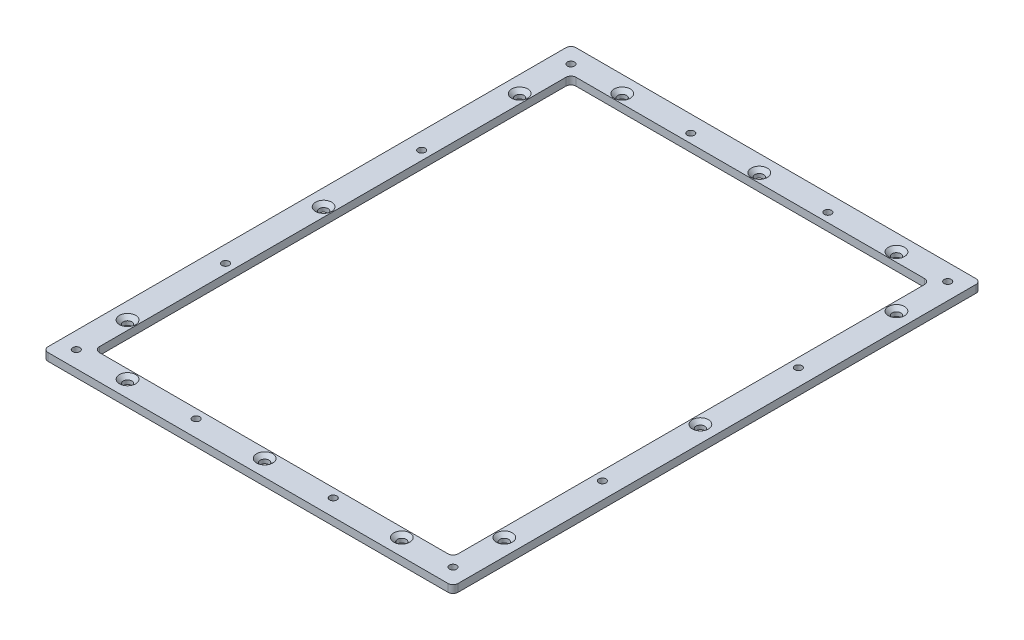
SolidWorks part; units mm, degrees
ref_plane "Front Plane" through (0, 0, 0) normal (0, 0, 1) x (1, 0, 0)
ref_plane "Top Plane" through (0, 0, 0) normal (0, 1, 0) x (1, 0, 0)
ref_plane "Right Plane" through (0, 0, 0) normal (1, 0, 0) x (0, 0, -1)
sketch "Sketch1" plane through (0, 0, 0) normal (0, 1, 0) x (1, 0, 0)
  line L0 (78, 103) -> (-78, 103) construction
  line L1 (-70, -93) -> (70, -93)
  line L2 (-70, -93) -> (-70, 93)
  line L3 (-70, 93) -> (70, 93)
  line L4 (70, -93) -> (70, 93)
  line L5 (-70, -93) -> (70, 93) construction
  line L6 (-70, 93) -> (70, -93) construction
  line L7 (80, -103) -> (-80, -103)
  line L8 (80, -103) -> (80, 103)
  line L9 (80, 103) -> (-80, 103)
  line L10 (-80, -103) -> (-80, 103)
  line L11 (80, -103) -> (-80, 103) construction
  line L12 (80, 103) -> (-80, -103) construction
  line L13 (-80, 101) -> (-80, -101) construction
  point P0 (0, 0)
  point P5 (0, 0)
  point P11 (-48.5964, 76.0062)
  point P12 (-80.7977, 104.555)
  dimension "D1" = 10
  dimension "D2" = 10
extrude "Boss-Extrude1" add sketch "Sketch1" along normal blind 3
ref_axis "Axis2" through (0, -0.3, 0) along (0, 1, 0)
fillet "Fillet1" radius 2 8 edges at (80, 1.5, -103) (80, 1.5, 103) (-80, 1.5, -103) (-80, 1.5, 103) (70, 1.5, -93) (70, 1.5, 93) (-70, 1.5, 93) (-70, 1.5, -93)
ref_plane "Plane1" through (78, 0, 0) normal (-1, 0, 0) x (0, 0, 1)
sketch "Sketch6" plane through (0, 0, 0) normal (0, -1, 0) x (1, 0, 0)
  line L9 (-78, -102) -> (78, -102)
  line L10 (79, -101) -> (79, 101)
  line L11 (78, 102) -> (-78, 102)
  line L12 (-79, 101) -> (-79, -101)
  line L13 (-78, -102) -> (78, -102)
  line L14 (79, -101) -> (79, 101)
  line L15 (78, 102) -> (-78, 102)
  line L16 (-79, 101) -> (-79, -101)
  line L21 (-78, -101.5) -> (78, -101.5)
  line L22 (78.5, -101) -> (78.5, 101)
  line L23 (78, 101.5) -> (-78, 101.5)
  line L24 (-78.5, 101) -> (-78.5, -101)
  line L25 (-78, -101.5) -> (78, -101.5)
  line L26 (78.5, -101) -> (78.5, 101)
  line L27 (78, 101.5) -> (-78, 101.5)
  line L28 (-78.5, 101) -> (-78.5, -101)
  arc A8 (78, -102) -> (79, -101) centre (78, -101) ccw
  arc A9 (79, 101) -> (78, 102) centre (78, 101) ccw
  arc A10 (-78, 102) -> (-79, 101) centre (-78, 101) ccw
  arc A11 (-79, -101) -> (-78, -102) centre (-78, -101) ccw
  arc A12 (78, -102) -> (79, -101) centre (78, -101) ccw
  arc A13 (79, 101) -> (78, 102) centre (78, 101) ccw
  arc A14 (-78, 102) -> (-79, 101) centre (-78, 101) ccw
  arc A15 (-79, -101) -> (-78, -102) centre (-78, -101) ccw
  arc A20 (78, -101.5) -> (78.5, -101) centre (78, -101) ccw
  arc A21 (78, -101.5) -> (78.5, -101) centre (78, -101) ccw
  arc A22 (78.5, 101) -> (78, 101.5) centre (78, 101) ccw
  arc A23 (78.5, 101) -> (78, 101.5) centre (78, 101) ccw
  arc A24 (-78, 101.5) -> (-78.5, 101) centre (-78, 101) ccw
  arc A25 (-78, 101.5) -> (-78.5, 101) centre (-78, 101) ccw
  arc A26 (-78.5, -101) -> (-78, -101.5) centre (-78, -101) ccw
  arc A27 (-78.5, -101) -> (-78, -101.5) centre (-78, -101) ccw
  dimension "D1" = 1
  dimension "D2" = 1.5
extrude "Boss-Extrude3" add sketch "Sketch6" along normal blind 0.5
fillet "Fillet2" radius 0.25 32 edges at (-79, -0.5, 0) (-78.7071, -0.5, 101.7071) (0, -0.5, 102) (78.7071, -0.5, 101.7071) (79, -0.5, 0) (78.7071, -0.5, -101.7071) (0, -0.5, -102) (-78.5, -0.5, 0) (-78.3536, -0.5, 101.3536) (0, -0.5, 101.5) (78.3536, -0.5, 101.3536) (78.5, -0.5, 0) (78.3536, -0.5, -101.3536) (0, -0.5, -101.5) (-78.3536, 0, -101.3536) (-78.5, 0, 0) (-78.3536, 0, 101.3536) (0, 0, 101.5) (78.3536, 0, 101.3536) (78.5, 0, 0) (78.3536, 0, -101.3536) (-78.7071, 0, -101.7071) (-79, 0, 0) (-78.7071, 0, 101.7071) (0, 0, 102) (78.7071, 0, 101.7071) (79, 0, 0) (78.7071, 0, -101.7071) (-78.7071, -0.5, -101.7071) (-78.3536, -0.5, -101.3536) (0, 0, -101.5) (0, 0, -102)
sketch "Sketch10" plane through (0, 3, 0) normal (0, 1, 0) x (1, 0, 0)
  line L0 (-53.5, 96.5) -> (0, 96.5) construction
  line L1 (0, 96.5) -> (53.5, 96.5) construction
  line L2 (-73.5, 76.5) -> (-73.5, 0) construction
  line L3 (-73.5, 0) -> (-73.5, -76.5) construction
  line L4 (-53.5, -96.5) -> (0, -96.5) construction
  line L5 (0, -96.5) -> (53.5, -96.5) construction
  line L6 (73.5, 76.5) -> (73.5, 0) construction
  line L7 (73.5, 0) -> (73.5, -76.5) construction
  line L8 (-73.5, 76.5) -> (-73.5, 96.5) construction
  line L9 (-73.5, 96.5) -> (-53.5, 96.5) construction
  line L10 (0, 0) -> (0, 43.7963) construction
  line L11 (0, 0) -> (39.7562, 0) construction
  circle A0 centre (0, 96.5) radius 1.7 construction
  circle A1 centre (-53.5, 96.5) radius 1.7 construction
  circle A2 centre (-73.5, 76.5) radius 1.7 construction
  circle A3 centre (-73.5, 0) radius 1.7 construction
  circle A4 centre (-73.5, -76.5) radius 1.7 construction
  circle A5 centre (-53.5, -96.5) radius 1.7 construction
  circle A6 centre (0, -96.5) radius 1.7 construction
  circle A7 centre (53.5, -96.5) radius 1.7 construction
  circle A8 centre (73.5, -76.5) radius 1.7 construction
  circle A9 centre (73.5, 0) radius 1.7 construction
  circle A10 centre (73.5, 76.5) radius 1.7 construction
  circle A11 centre (53.5, 96.5) radius 1.7 construction
  circle A12 centre (0, 96.5) radius 1.7
  circle A13 centre (-53.5, 96.5) radius 1.7
  circle A14 centre (-73.5, 76.5) radius 1.7
  circle A15 centre (-73.5, 0) radius 1.7
  circle A16 centre (-73.5, -76.5) radius 1.7
  circle A17 centre (-53.5, -96.5) radius 1.7
  circle A18 centre (0, -96.5) radius 1.7
  circle A19 centre (53.5, -96.5) radius 1.7
  circle A20 centre (73.5, -76.5) radius 1.7
  circle A21 centre (73.5, 0) radius 1.7
  circle A22 centre (73.5, 76.5) radius 1.7
  circle A23 centre (53.5, 96.5) radius 1.7
  circle A24 centre (73.5, -38.25) radius 1.4
  circle A25 centre (73.5, 38.25) radius 1.4
  circle A26 centre (26.75, 96.5) radius 1.4
  circle A27 centre (-26.75, 96.5) radius 1.4
  circle A28 centre (-73.5, 38.25) radius 1.4
  circle A29 centre (-73.5, -38.25) radius 1.4
  circle A30 centre (-26.75, -96.5) radius 1.4
  circle A31 centre (26.75, -96.5) radius 1.4
  circle A32 centre (-73.5, 96.5) radius 1.4
  circle A33 centre (73.5, 96.5) radius 1.4
  circle A34 centre (73.5, -96.5) radius 1.4
  circle A35 centre (-73.5, -96.5) radius 1.4
  dimension "D1" = 2.8
extrude "Cut-Extrude1" cut sketch "Sketch10" against normal through all
hole_wizard "CSK for M3 Flat Head Machine Screw2" positions "3DSketch3" profile "Sketch11" countersink size "M3" standard "ANSI Metric" end condition through all
sketch3d "3DSketch3"
  line L0 (-53.5, 0, -96.5) -> (-53.5, 3, -96.5) construction
  line L1 (0, 0, -96.5) -> (0, 3, -96.5) construction
  line L2 (-73.5, 0, -76.5) -> (-73.5, 3, -76.5) construction
  line L3 (53.5, 0, -96.5) -> (53.5, 3, -96.5) construction
  line L4 (73.5, 0, -76.5) -> (73.5, 3, -76.5) construction
  line L5 (73.5, 0, 0) -> (73.5, 3, 0) construction
  line L6 (73.5, 0, 76.5) -> (73.5, 3, 76.5) construction
  line L7 (53.5, 0, 96.5) -> (53.5, 3, 96.5) construction
  line L8 (0, 0, 96.5) -> (0, 3, 96.5) construction
  line L9 (-53.5, 0, 96.5) -> (-53.5, 3, 96.5) construction
  line L10 (-73.5, 0, 76.5) -> (-73.5, 3, 76.5) construction
  line L11 (-73.5, 0, 0) -> (-73.5, 3, 0) construction
  point P0 (-53.5, 3, -96.5)
  point P4 (0, 3, -96.5)
  point P8 (-73.5, 3, -76.5)
  point P12 (53.5, 3, -96.5)
  point P16 (73.5, 3, -76.5)
  point P20 (73.5, 3, 0)
  point P28 (53.5, 3, 96.5)
  point P32 (0, 3, 96.5)
  point P36 (-53.5, 3, 96.5)
  point P40 (-73.5, 3, 76.5)
  point P44 (73.5, 3, 76.5)
  point P46 (-73.5, 3, 0)
  point P51 (0, 0, 0)
sketch "Sketch11" plane through (-53.5, 3, -96.5) normal (1, 0, 0) x (0, 0, 1)
  line L0 (0, 0) -> (0, 3.5)
  line L1 (0, 3.5) -> (1.725, 3.5)
  line L2 (1.7, 3.475) -> (1.7, 1.45)
  line L3 (1.7, 1.45) -> (3.15, 0)
  line L5 (3.15, 0) -> (0, 0)
  line L6 (-1.7, 1.45) -> (-3.15, 0) construction
  line L7 (1.725, 3.5) -> (1.7, 3.475)
  line L8 (-1.725, 3.5) -> (-1.7, 3.475) construction
  line L11 (0, -6.35) -> (0, 107.95) construction
  dimension "Thru Hole Dia." = 3.4
  dimension "Thru Hole Depth" = 3.5
  dimension "Near C'Sink Dia." = 6.3
  dimension "Near C'Sink Angle" = 90
  dimension "Far C'Sink Dia." = 3.45
  dimension "Far C'Sink Angle" = 90
sketch "Sketch12" plane through (0, 0, 0) normal (0, -1, 0) x (1, 0, 0)
  line L0 (78, -102.25) -> (-78, -102.25) construction
  line L1 (79.25, 101) -> (79.25, -101) construction
  line L2 (-79.25, -101) -> (-79.25, 101) construction
  line L3 (-78, 102.25) -> (78, 102.25) construction
  line L4 (78, -102.25) -> (-78, -102.25)
  line L5 (79.25, 101) -> (79.25, -101)
  line L6 (-79.25, -101) -> (-79.25, 101)
  line L7 (-78, 102.25) -> (78, 102.25)
  line L9 (-249.5654, 283.7441) -> (249.5654, 283.7441)
  line L10 (-249.5654, 283.7441) -> (-249.5654, -283.7441)
  line L11 (-249.5654, -283.7441) -> (249.5654, -283.7441)
  line L12 (249.5654, 283.7441) -> (249.5654, -283.7441)
  line L13 (-249.5654, 283.7441) -> (249.5654, -283.7441) construction
  line L14 (-249.5654, -283.7441) -> (249.5654, 283.7441) construction
  arc A0 (-79.25, -101) -> (-78, -102.25) centre (-78, -101) ccw construction
  arc A1 (78, -102.25) -> (79.25, -101) centre (78, -101) ccw construction
  arc A2 (79.25, 101) -> (78, 102.25) centre (78, 101) ccw construction
  arc A3 (-78, 102.25) -> (-79.25, 101) centre (-78, 101) ccw construction
  arc A4 (-79.25, -101) -> (-78, -102.25) centre (-78, -101) ccw
  arc A5 (78, -102.25) -> (79.25, -101) centre (78, -101) ccw
  arc A6 (79.25, 101) -> (78, 102.25) centre (78, 101) ccw
  arc A7 (-78, 102.25) -> (-79.25, 101) centre (-78, 101) ccw
  point P4 (0, 0)
extrude "Cut-Extrude2" [suppressed] cut sketch "Sketch12" against normal through all
